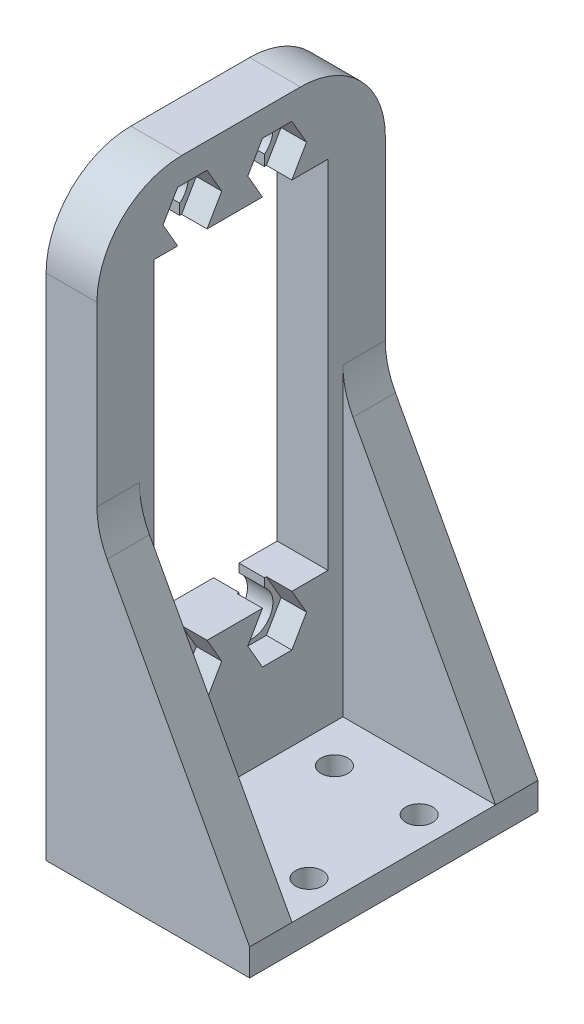
SolidWorks part; units mm, degrees
ref_plane "Front Plane" through (0, 0, 0) normal (0, 0, 1) x (1, 0, 0)
ref_plane "Top Plane" through (0, 0, 0) normal (0, 1, 0) x (1, 0, 0)
ref_plane "Right Plane" through (0, 0, 0) normal (1, 0, 0) x (0, 0, -1)
sketch "Sketch1" plane through (0, 0, 0) normal (1, 0, 0) x (0, 0, -1)
  line L0 (-16.25, -40) -> (-16.25, 30)
  line L1 (-9.5, -21) -> (11, -21)
  line L2 (-9.5, -21) -> (-9.5, 21)
  line L3 (-9.5, 21) -> (11, 21)
  line L4 (11, -21) -> (11, 21)
  line L5 (-9.5, -21) -> (11, 21) construction
  line L6 (-9.5, 21) -> (11, -21) construction
  line L7 (-16.25, 30) -> (17.75, 30)
  line L8 (17.75, 30) -> (17.75, -40)
  line L10 (-16.25, -40) -> (17.75, -40)
  line L11 (23, -40) -> (-23, -40) construction
  point P0 (0, 0)
  point P10 (0.75, 21)
  point P11 (0.75, 30)
  dimension "D1" = 42
  dimension "D2" = 20.5
  dimension "D3" = 30
  dimension "D4" = 9
  dimension "D5" = 34
extrude "Boss-Extrude1" add sketch "Sketch1" along normal mid plane 6 contours L1 L4 L3 L2 | L8 L10 L0 L7 region at (0, 0, -0.75)
sketch "Sketch2" plane through (-3, 0, 0) normal (-1, 0, 0) x (0, 0, 1)
  line L0 (3.5, -21) -> (6.5, -21)
  line L1 (9.5, -21) -> (-11, -21) construction
  line L2 (9.5, 21) -> (-11, 21) construction
  line L5 (-6.5, -21) -> (-3.5, -21)
  line L6 (-6.5, -21) -> (-6.5, -22)
  line L7 (-3.5, -21) -> (-3.5, -22)
  line L8 (3.5, -21) -> (3.5, -22)
  line L9 (6.5, -21) -> (6.5, -22)
  line L11 (6.5, 21) -> (6.5, 22.26)
  line L13 (3.5, 21) -> (3.5, 22.26)
  line L14 (-3.5, 21) -> (-3.5, 22.26)
  line L16 (-6.5, 21) -> (-6.5, 22.26)
  line L17 (-6.5, 21) -> (-3.5, 21)
  line L18 (3.5, 21) -> (6.5, 21)
  arc A0 (6.5, -22) -> (3.5, -22) centre (5, -24) cw
  arc A1 (-3.5, -22) -> (-6.5, -22) centre (-5, -24) cw
  arc A2 (-3.5, 22.26) -> (-6.5, 22.26) centre (-5, 24.26) ccw
  arc A3 (6.5, 22.26) -> (3.5, 22.26) centre (5, 24.26) ccw
  dimension "D1" = 48.26
  dimension "D2" = 48.26
extrude "Cut-Extrude1" cut sketch "Sketch2" against normal through all
sketch "Sketch3" plane through (3, 0, 0) normal (1, 0, 0) x (0, 0, -1)
  line L0 (-16.25, 30) -> (17.75, 30) construction
  line L1 (-9.5, 0) -> (11, 0) construction
  line L2 (-9.5, -21) -> (-9.5, 21) construction
  line L3 (-3.2679, 27) -> (-6.7321, 27)
  line L4 (11, -21) -> (11, 21) construction
  line L5 (0, 21) -> (0, -21) construction
  line L6 (-6.7321, 27) -> (-8.4641, 24)
  line L7 (-8.4641, 24) -> (-6.7321, 21)
  line L8 (-6.7321, 21) -> (-3.2679, 21)
  line L9 (-3.2679, 21) -> (-1.5359, 24)
  line L10 (-1.5359, 24) -> (-3.2679, 27)
  line L14 (-9.5, -21) -> (-6.5, -21) construction
  line L17 (1.5359, 24) -> (3.2679, 27)
  line L18 (3.2679, 21) -> (1.5359, 24)
  line L19 (6.7321, 21) -> (3.2679, 21)
  line L20 (8.4641, 24) -> (6.7321, 21)
  line L21 (6.7321, 27) -> (8.4641, 24)
  line L22 (3.2679, 27) -> (6.7321, 27)
  line L23 (-3.2679, 27) -> (-6.7321, 27)
  line L24 (-6.7321, 27) -> (-8.4641, 24)
  line L25 (-8.4641, 24) -> (-6.7321, 21)
  line L26 (-6.7321, 21) -> (-3.2679, 21)
  line L27 (-3.2679, 21) -> (-1.5359, 24)
  line L28 (-1.5359, 24) -> (-3.2679, 27)
  line L29 (1.5359, 24) -> (3.2679, 27)
  line L30 (3.2679, 21) -> (1.5359, 24)
  line L31 (6.7321, 21) -> (3.2679, 21)
  line L32 (8.4641, 24) -> (6.7321, 21)
  line L33 (6.7321, 27) -> (8.4641, 24)
  line L34 (3.2679, 27) -> (6.7321, 27)
  line L35 (-3.2679, 27) -> (-6.7321, 27)
  line L36 (-6.7321, 27) -> (-8.4641, 24)
  line L37 (-8.4641, 24) -> (-6.7321, 21)
  line L38 (-6.7321, 21) -> (-3.2679, 21)
  line L39 (-3.2679, 21) -> (-1.5359, 24)
  line L40 (-1.5359, 24) -> (-3.2679, 27)
  line L41 (1.5359, 24) -> (3.2679, 27)
  line L42 (3.2679, 21) -> (1.5359, 24)
  line L43 (6.7321, 21) -> (3.2679, 21)
  line L44 (8.4641, 24) -> (6.7321, 21)
  line L45 (6.7321, 27) -> (8.4641, 24)
  line L46 (3.2679, 27) -> (6.7321, 27)
  line L47 (-3.2679, 27) -> (-6.7321, 27)
  line L48 (-6.7321, 27) -> (-8.4641, 24)
  line L49 (-8.4641, 24) -> (-6.7321, 21)
  line L50 (-6.7321, 21) -> (-3.2679, 21)
  line L51 (-3.2679, 21) -> (-1.5359, 24)
  line L52 (-1.5359, 24) -> (-3.2679, 27)
  line L53 (1.5359, 24) -> (3.2679, 27)
  line L54 (3.2679, 21) -> (1.5359, 24)
  line L55 (6.7321, 21) -> (3.2679, 21)
  line L56 (8.4641, 24) -> (6.7321, 21)
  line L57 (6.7321, 27) -> (8.4641, 24)
  line L58 (3.2679, 27) -> (6.7321, 27)
  line L59 (3.2679, -27) -> (6.7321, -27)
  line L60 (6.7321, -27) -> (8.4641, -24)
  line L61 (8.4641, -24) -> (6.7321, -21)
  line L62 (6.7321, -21) -> (3.2679, -21)
  line L63 (3.2679, -21) -> (1.5359, -24)
  line L64 (1.5359, -24) -> (3.2679, -27)
  line L65 (-1.5359, -24) -> (-3.2679, -27)
  line L66 (-3.2679, -21) -> (-1.5359, -24)
  line L67 (-6.7321, -21) -> (-3.2679, -21)
  line L68 (-8.4641, -24) -> (-6.7321, -21)
  line L69 (-6.7321, -27) -> (-8.4641, -24)
  line L70 (-3.2679, -27) -> (-6.7321, -27)
  line L71 (3.2679, -27) -> (6.7321, -27)
  line L72 (6.7321, -27) -> (8.4641, -24)
  line L73 (8.4641, -24) -> (6.7321, -21)
  line L74 (6.7321, -21) -> (3.2679, -21)
  line L75 (3.2679, -21) -> (1.5359, -24)
  line L76 (1.5359, -24) -> (3.2679, -27)
  line L77 (-1.5359, -24) -> (-3.2679, -27)
  line L78 (-3.2679, -21) -> (-1.5359, -24)
  line L79 (-6.7321, -21) -> (-3.2679, -21)
  line L80 (-8.4641, -24) -> (-6.7321, -21)
  line L81 (-6.7321, -27) -> (-8.4641, -24)
  line L82 (-3.2679, -27) -> (-6.7321, -27)
  line L83 (3.2679, -27) -> (6.7321, -27)
  line L84 (6.7321, -27) -> (8.4641, -24)
  line L85 (8.4641, -24) -> (6.7321, -21)
  line L86 (6.7321, -21) -> (3.2679, -21)
  line L87 (3.2679, -21) -> (1.5359, -24)
  line L88 (1.5359, -24) -> (3.2679, -27)
  line L89 (-1.5359, -24) -> (-3.2679, -27)
  line L90 (-3.2679, -21) -> (-1.5359, -24)
  line L91 (-6.7321, -21) -> (-3.2679, -21)
  line L92 (-8.4641, -24) -> (-6.7321, -21)
  line L93 (-6.7321, -27) -> (-8.4641, -24)
  line L94 (-3.2679, -27) -> (-6.7321, -27)
  line L95 (3.2679, -27) -> (6.7321, -27)
  line L96 (6.7321, -27) -> (8.4641, -24)
  line L97 (8.4641, -24) -> (6.7321, -21)
  line L98 (6.7321, -21) -> (3.2679, -21)
  line L99 (3.2679, -21) -> (1.5359, -24)
  line L100 (1.5359, -24) -> (3.2679, -27)
  line L101 (-1.5359, -24) -> (-3.2679, -27)
  line L102 (-3.2679, -21) -> (-1.5359, -24)
  line L103 (-6.7321, -21) -> (-3.2679, -21)
  line L104 (-8.4641, -24) -> (-6.7321, -21)
  line L105 (-6.7321, -27) -> (-8.4641, -24)
  line L106 (-3.2679, -27) -> (-6.7321, -27)
  arc M10 (3.5, 22.26) -> (6.5, 22.26) centre (5, 24.26) cw
  line M14 (11, -21) -> (6.5, -21)
  line M22 (-6.5, -21) -> (-9.5, -21)
  arc M26 (-6.5, 22.26) -> (-3.5, 22.26) centre (-5, 24.26) cw
  line M45 (6.5, -21) -> (6.5, -22)
  arc M46 (6.5, -22) -> (3.5, -22) centre (5, -24) cw
  line M47 (3.5, -22) -> (3.5, -21)
  line M49 (-3.5, -21) -> (-3.5, -22)
  arc M50 (-3.5, -22) -> (-6.5, -22) centre (-5, -24) cw
  line M51 (-6.5, -22) -> (-6.5, -21)
  line M54 (3.5, -21) -> (-3.5, -21)
  dimension "D1" = 6
extrude "Cut-Extrude2" cut sketch "Sketch3" against normal blind 3 contours L9 L10 L3 L6 L7 M26 | L22 L17 L18 L20 L21 M10 | L70 L65 L66 L68 L69 M54 M49 M50 M51 M22 | L63 L64 L59 L60 L61 M14 M45 M46 M47 M54 region at (3, 24, 5) region at (3, 24, -5) region at (3, -25.4542, -2.4813) region at (3, -22.5458, 2.4813)
sketch "Sketch4" plane through (0, -40, 0) normal (0, -1, 0) x (1, 0, 0)
  line L0 (-3, 16.25) -> (-3, -17.75)
  line L1 (-3, 16.25) -> (-3, -17.75) construction
  line L2 (-3, -17.75) -> (21, -17.75)
  line L3 (21, -17.75) -> (21, 16.25)
  line L4 (21, -0.75) -> (-3, -0.75) construction
  line L5 (1, -13.75) -> (-3, -13.75) construction
  line L6 (1, -13.75) -> (1, -17.75) construction
  line L7 (17, -13.75) -> (21, -13.75) construction
  line L8 (17, 12.25) -> (21, 12.25) construction
  line L9 (1, 12.25) -> (1, 16.25) construction
  line L10 (1, 12.25) -> (-3, 12.25) construction
  line L11 (-3, 16.25) -> (21, 16.25)
  dimension "D1" = 17
  dimension "D2" = 4
  dimension "D4" = 16
extrude "Boss-Extrude2" add sketch "Sketch4" against normal blind 3.175 contours L2 L3 L11 L0
sketch "Sketch5" plane through (0, 0, -17.75) normal (0, 0, -1) x (-1, 0, 0)
  line L0 (-3, -36.825) -> (-21, -36.825)
  line L1 (-21, -36.825) -> (-3, -3.4125)
  line L2 (-3, 30) -> (-3, -36.825) construction
  line L3 (-3, -3.4125) -> (-3, -36.825)
sketch "Sketch6" plane through (0, 0, 16.25) normal (0, 0, 1) x (1, 0, 0)
  line L0 (21, -36.825) -> (3, -36.825)
  line L1 (3, -36.825) -> (3, -3.4125)
  line L2 (3, -36.825) -> (3, 30) construction
  line L3 (3, -3.4125) -> (21, -36.825)
extrude "Boss-Extrude3" add sketch "Sketch5" against normal blind 5
extrude "Boss-Extrude4" add sketch "Sketch6" against normal blind 5
hole_wizard "1/8 (0.125) Diameter Hole1" positions "Sketch7" profile "Sketch8" hole size "1/8" standard "ANSI Inch" end condition through all
sketch "Sketch7" plane through (0, -36.825, 0) normal (0, 1, 0) x (1, 0, 0)
  line L0 (21, 12.75) -> (3, 12.75) construction
  line L4 (21, 12.75) -> (21, -11.25) construction
  point P0 (7.5, 7.25)
  point P2 (17.5, 7.25)
  point P4 (17.5, -5.75)
  point P6 (7.5, -5.75)
  dimension "D1" = 10
  dimension "D2" = 13
  dimension "D3" = 10
  dimension "D4" = 5.5
  dimension "D5" = 3.5
sketch "Sketch8" plane through (7.5, -36.825, -7.25) normal (1, 0, 0) x (0, 0, 1)
  line L0 (0, 0) -> (0, 3.175)
  line L1 (0, 3.175) -> (1.5875, 3.175)
  line L2 (1.5875, 3.175) -> (1.5875, 0)
  line L5 (1.5875, 0) -> (0, 0)
  line L11 (0, -6.35) -> (0, 107.95) construction
  dimension "Thru Hole Dia." = 3.175
  dimension "Thru Hole Depth" = 3.175
fillet "Fillet1" radius 10 2 edges at (0, 30, -17.75) (0, 30, 16.25)
fillet "Fillet2" radius 10 2 edges at (3, -3.4125, -15.25) (3, -3.4125, 13.75)
